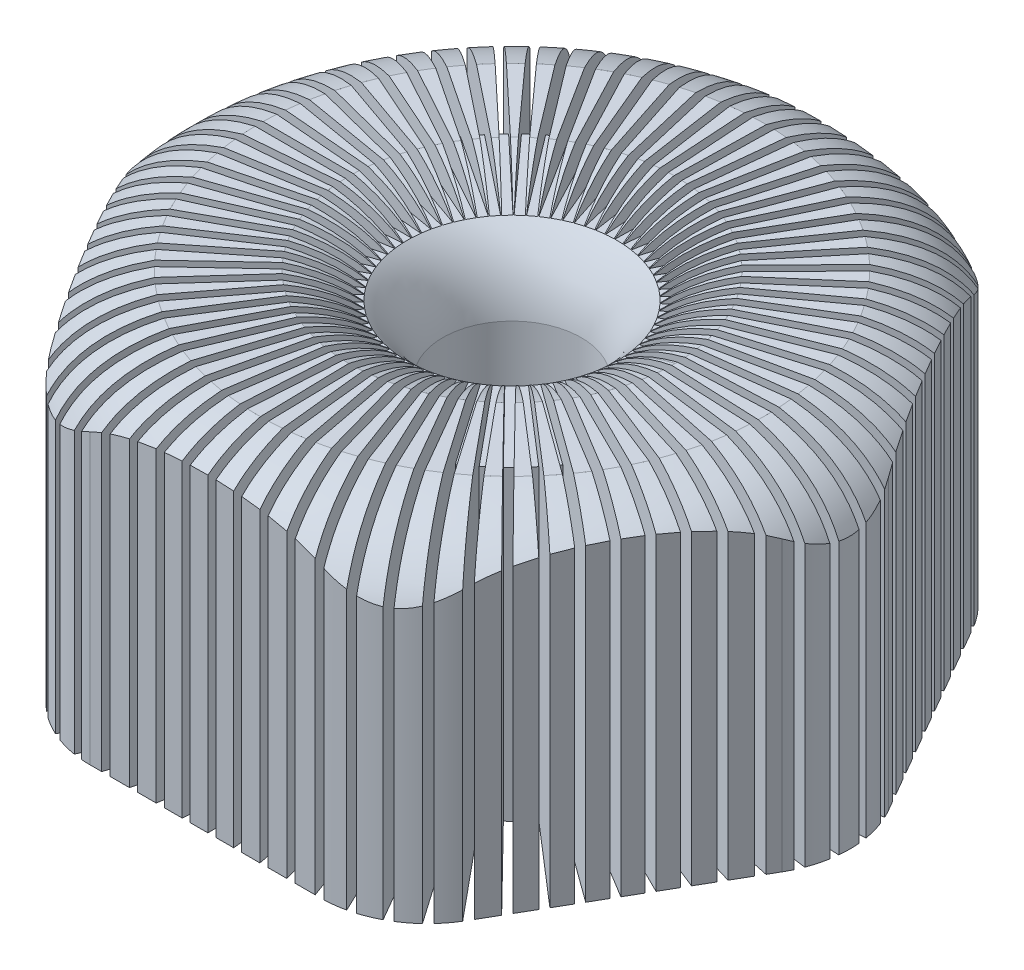
SolidWorks part; units mm, degrees
ref_plane "Front Plane" through (0, 0, 0) normal (0, 0, 1) x (1, 0, 0)
ref_plane "Top Plane" through (0, 0, 0) normal (0, 1, 0) x (1, 0, 0)
ref_plane "Right Plane" through (0, 0, 0) normal (1, 0, 0) x (0, 0, -1)
sketch "Sketch1" plane through (0, 0, 0) normal (0, 1, 0) x (1, 0, 0)
  line L1 (60.6218, 10) -> (38.9711, 47.5)
  line L2 (21.6506, 57.5) -> (-21.6506, 57.5)
  line L3 (-38.9711, 47.5) -> (-60.6218, 10)
  line L4 (-60.6218, -10) -> (-38.9711, -47.5)
  line L5 (-21.6506, -57.5) -> (21.6506, -57.5)
  line L6 (38.9711, -47.5) -> (60.6218, -10)
  circle A0 centre (0, 0) radius 57.5 construction
  arc A1 (-21.6506, -57.5) -> (-38.9711, -47.5) centre (-21.6506, -37.5) cw
  arc A2 (21.6506, -57.5) -> (38.9711, -47.5) centre (21.6506, -37.5) ccw
  arc A3 (60.6218, -10) -> (60.6218, 10) centre (43.3013, 0) ccw
  arc A4 (38.9711, 47.5) -> (21.6506, 57.5) centre (21.6506, 37.5) ccw
  arc A5 (-21.6506, 57.5) -> (-38.9711, 47.5) centre (-21.6506, 37.5) ccw
  arc A6 (-60.6218, -10) -> (-60.6218, 10) centre (-43.3013, 0) cw
  dimension "D1" = 115
  dimension "D2" = 20
extrude "Boss-Extrude2" add sketch "Sketch1" along normal blind 62.5
sketch "Sketch6" plane through (0, 62.5, 0) normal (0, 1, 0) x (1, 0, 0)
  circle A0 centre (0, 0) radius 13
extrude "Cut-Extrude1" cut sketch "Sketch6" against normal up to surface (62.5 mm away) up to face at (0, 0, 0)
sketch "Sketch7" plane through (0, 0, 0) normal (0, 0, 1) x (1, 0, 0)
  line L0 (0, 62.5) -> (0, 0) construction
  line L1 (-21.6506, 62.5) -> (21.6506, 62.5) construction
  line L2 (0, 62.5) -> (13, 62.5) construction
  line L3 (13, 62.5) -> (13, 45)
  line L4 (13, 62.5) -> (30.5, 62.5)
  line L5 (38.9711, 62.5) -> (21.6506, 62.5) construction
  line L6 (13, 0) -> (63.3013, 0) construction
  line L7 (38.9711, 0) -> (38.9711, 62.5) construction
  line L8 (64.9423, 62.5) -> (47.4423, 62.5)
  line L9 (64.9423, 62.5) -> (64.9423, 45)
  line L10 (13, 62.5) -> (-13, 62.5) construction
  line L11 (13, 62.5) -> (18.1614, 56.1261) construction
  spline S0 degree 2 poles (13, 45) (15.1116, 59.0525) (30.5, 62.5) knots 0 0 0 1 1 1
  spline S1 degree 2 poles (64.9423, 45) (62.8306, 59.0525) (47.4423, 62.5) knots 0 0 0 1 1 1
  dimension "D1" = 13
  dimension "D2" = 17.5
  dimension "D3" = 17.5
  dimension "D4" = 8.2017
revolve "Cut-Revolve1" cut sketch "Sketch7" angle 360 about L0
ref_plane "Plane1" through (0, 31.25, 0) normal (0, 1, 0) x (1, 0, 0)
sketch "Sketch8" plane through (0, 0, 0) normal (0, 0, 1) x (1, 0, 0)
  line L0 (-63.3013, 62.5) -> (-63.3013, 0)
  line L1 (-13.3013, 5) -> (-38.3013, 5) construction
  line L2 (-38.3013, 5) -> (-38.3013, 0)
  line L3 (-63.3013, 0) -> (-38.3013, 0)
  line L4 (-13.3013, 0) -> (-13.3013, 5) construction
  line L5 (-38.3013, 5) -> (-38.3013, 57.5)
  line L6 (63.25, 31.25) -> (-63.25, 31.25) construction
  line L7 (-63.3013, 31.25) -> (-38.3013, 31.25) construction
  line L8 (-13.3013, 62.5) -> (-13.3013, 57.5)
  line L9 (-63.3013, 62.5) -> (-13.3013, 62.5)
  line L10 (-13.3013, 57.5) -> (-38.3013, 57.5)
  line L11 (-38.3013, 0) -> (-13.3013, 0) construction
  point P3 (-66.188, 24)
  dimension "D1" = 50
  dimension "D2" = 50
  dimension "D3" = 5
  dimension "D4" = 25
extrude "Cut-Extrude2" cut sketch "Sketch8" against normal blind 0.75 and the other way blind 0.75
pattern_circular "CirPattern1" count 75 over 360 about axis through (0, -36.7696, 0) along (0, 1, 0) of "Cut-Extrude2"
